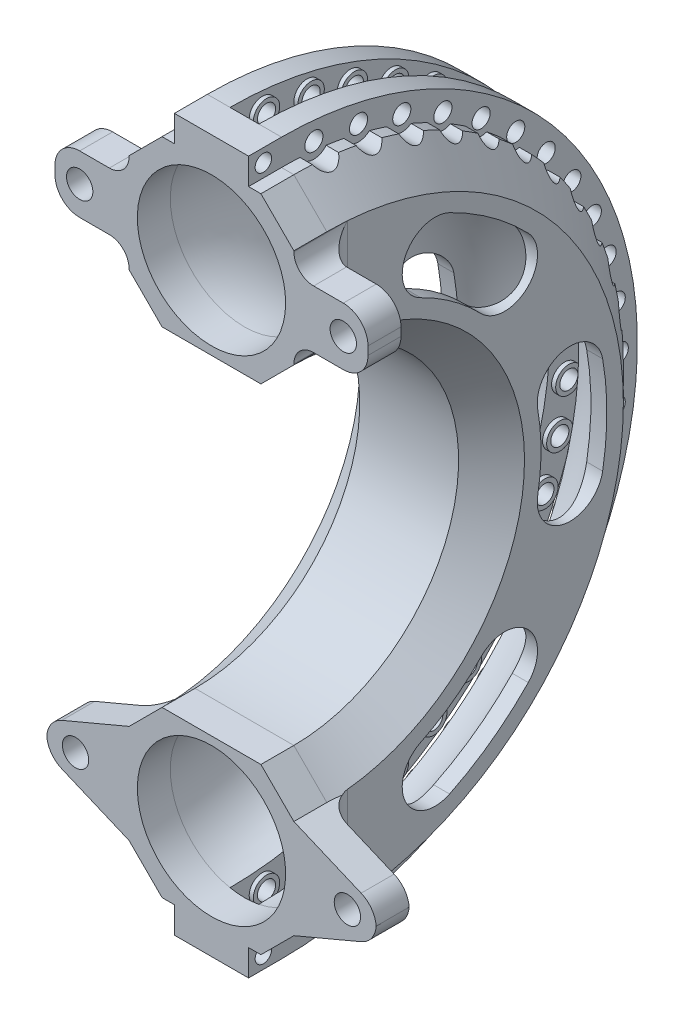
SolidWorks part; units mm, degrees
material "ABS"
ref_plane "前视基准面" through (0, 0, 0) normal (0, 0, 1) x (1, 0, 0)
ref_plane "上视基准面" through (0, 0, 0) normal (0, 1, 0) x (1, 0, 0)
ref_plane "右视基准面" through (0, 0, 0) normal (1, 0, 0) x (0, 0, -1)
sketch "草图1" plane through (0, 0, 0) normal (0, 0, 1) x (1, 0, 0)
  line L0 (0, 30) -> (0, -30) construction
  line L1 (0, 0) -> (57.2515, 0) construction
  line L2 (-10, 40) -> (10, 40)
  line L3 (-10, 40) -> (-10, 20)
  line L4 (-10, 20) -> (10, 20)
  line L5 (10, 40) -> (10, 20)
  line L6 (-10, 40) -> (10, 20) construction
  line L7 (-10, 20) -> (10, 40) construction
  circle A0 centre (0, 30) radius 9
  dimension "D2" = 18
  dimension "D1" = 60
  dimension "D3" = 20
sketch "草图2" plane through (0, 0, 0) normal (1, 0, 0) x (0, 0, -1)
  line L0 (0, 40) -> (0, 20) construction
  arc A0 (0, 30) -> (0, -30) centre (0, 0) cw
sweep "扫描2" add profiles "草图1" path "草图2"
chamfer "倒角1" distance 4 angle 45 4 edges at (-10, 0, -40) (-10, 0, -20) (10, 0, -20) (10, 0, -40)
sketch "草图9" plane through (0, 0, 0) normal (1, 0, 0) x (0, 0, -1)
  line L0 (0, 40) -> (0, 43.2)
  line L2 (0, -43.2) -> (0, -40)
  arc A0 (0, -43.2) -> (0, 43.2) centre (0, 0) ccw
  arc A1 (0, -40) -> (0, 40) centre (0, 0) ccw construction
  arc A2 (0, -40) -> (0, 40) centre (0, 0) ccw
  dimension "D1" = 3.2
extrude "凸台-拉伸1" add sketch "草图9" along normal blind 4.5 and the other way blind 4.5
sketch "草图10" plane through (0, 0, 0) normal (1, 0, 0) x (0, 0, -1)
  circle A0 centre (0, 0) radius 31.3466
  circle A1 centre (0, 0) radius 43.2
  arc A2 (0, -43.2) -> (0, 43.2) centre (0, 0) ccw construction
  dimension "D1" = 11.8534
extrude "切除-拉伸1" cut sketch "草图10" against normal blind 1.75 and the other way blind 1.75
sketch "草图11" plane through (0, 0, 0) normal (1, 0, 0) x (0, 0, -1)
  line L0 (3.9297, 40.8112) -> (0, 0) construction
  line L1 (0, 0) -> (0, 59.689) construction
  line L2 (0, 0) -> (3.9297, 40.8112) construction
  line L3 (0, 0) -> (9.3497, 39.9197) construction
  circle A0 centre (3.9297, 40.8112) radius 1.1
  circle A1 centre (9.3497, 39.9197) radius 1.1
  circle A2 centre (14.6019, 38.3117) radius 1.1
  circle A3 centre (19.5921, 36.016) radius 1.1
  circle A4 centre (24.2306, 33.0738) radius 1.1
  circle A5 centre (28.4342, 29.5381) radius 1.1
  circle A6 centre (32.1274, 25.4722) radius 1.1
  circle A7 centre (35.244, 20.949) radius 1.1
  circle A8 centre (37.728, 16.0499) radius 1.1
  circle A9 centre (39.5348, 10.8627) radius 1.1
  circle A10 centre (40.6321, 5.4805) radius 1.1
  circle A11 centre (41, 0) radius 1.1
  circle A12 centre (40.6321, -5.4805) radius 1.1
  circle A13 centre (39.5348, -10.8627) radius 1.1
  circle A14 centre (37.728, -16.0499) radius 1.1
  circle A15 centre (35.244, -20.949) radius 1.1
  circle A16 centre (32.1274, -25.4722) radius 1.1
  circle A17 centre (28.4342, -29.5381) radius 1.1
  circle A18 centre (24.2306, -33.0738) radius 1.1
  circle A19 centre (19.5921, -36.016) radius 1.1
  circle A20 centre (14.6019, -38.3117) radius 1.1
  circle A21 centre (9.3497, -39.9197) radius 1.1
  circle A22 centre (3.9297, -40.8112) radius 1.1
  dimension "D1" = 2.2
  dimension "D2" = 41
  dimension "D3" = 5.5
  dimension "D4" = 23
extrude "切除-拉伸2" cut sketch "草图11" against normal through all both and the other way through all
sketch "草图12" plane through (4.5, 0, 0) normal (1, 0, 0) x (0, 0, -1)
  circle A0 centre (3.9297, -40.8112) radius 1.9
  circle A1 centre (3.9297, -40.8112) radius 1.1
  circle A2 centre (3.9297, -40.8112) radius 1.1 construction
  circle A3 centre (19.5921, 36.016) radius 1.1
  circle A4 centre (19.5921, 36.016) radius 1.1 construction
  circle A5 centre (14.6019, 38.3117) radius 1.1
  circle A6 centre (14.6019, 38.3117) radius 1.1 construction
  circle A7 centre (9.3497, 39.9197) radius 1.1
  circle A8 centre (9.3497, 39.9197) radius 1.1 construction
  circle A9 centre (3.9297, 40.8112) radius 1.1
  circle A10 centre (3.9297, 40.8112) radius 1.1 construction
  circle A11 centre (41, 0) radius 1.1
  circle A12 centre (41, 0) radius 1.1 construction
  circle A13 centre (40.6321, 5.4805) radius 1.1
  circle A14 centre (40.6321, 5.4805) radius 1.1 construction
  circle A15 centre (39.5348, 10.8627) radius 1.1
  circle A16 centre (39.5348, 10.8627) radius 1.1 construction
  circle A17 centre (37.728, 16.0499) radius 1.1
  circle A18 centre (37.728, 16.0499) radius 1.1 construction
  circle A19 centre (35.244, 20.949) radius 1.1
  circle A20 centre (35.244, 20.949) radius 1.1 construction
  circle A21 centre (32.1274, 25.4722) radius 1.1
  circle A22 centre (32.1274, 25.4722) radius 1.1 construction
  circle A23 centre (28.4342, 29.5381) radius 1.1
  circle A24 centre (28.4342, 29.5381) radius 1.1 construction
  circle A25 centre (24.2306, 33.0738) radius 1.1
  circle A26 centre (24.2306, 33.0738) radius 1.1 construction
  circle A27 centre (19.5921, -36.016) radius 1.1
  circle A28 centre (19.5921, -36.016) radius 1.1 construction
  circle A29 centre (24.2306, -33.0738) radius 1.1
  circle A30 centre (24.2306, -33.0738) radius 1.1 construction
  circle A31 centre (28.4342, -29.5381) radius 1.1
  circle A32 centre (28.4342, -29.5381) radius 1.1 construction
  circle A33 centre (32.1274, -25.4722) radius 1.1
  circle A34 centre (32.1274, -25.4722) radius 1.1 construction
  circle A35 centre (35.244, -20.949) radius 1.1
  circle A36 centre (35.244, -20.949) radius 1.1 construction
  circle A37 centre (37.728, -16.0499) radius 1.1
  circle A38 centre (37.728, -16.0499) radius 1.1 construction
  circle A39 centre (39.5348, -10.8627) radius 1.1
  circle A40 centre (39.5348, -10.8627) radius 1.1 construction
  circle A41 centre (40.6321, -5.4805) radius 1.1
  circle A42 centre (40.6321, -5.4805) radius 1.1 construction
  circle A43 centre (9.3497, -39.9197) radius 1.1
  circle A44 centre (9.3497, -39.9197) radius 1.1 construction
  circle A45 centre (14.6019, -38.3117) radius 1.1
  circle A46 centre (14.6019, -38.3117) radius 1.1 construction
  circle A47 centre (19.5921, 36.016) radius 1.9
  circle A48 centre (14.6019, 38.3117) radius 1.9
  circle A49 centre (9.3497, 39.9197) radius 1.9
  circle A50 centre (3.9297, 40.8112) radius 1.9
  circle A51 centre (41, 0) radius 1.9
  circle A52 centre (40.6321, 5.4805) radius 1.9
  circle A53 centre (39.5348, 10.8627) radius 1.9
  circle A54 centre (37.728, 16.0499) radius 1.9
  circle A55 centre (35.244, 20.949) radius 1.9
  circle A56 centre (32.1274, 25.4722) radius 1.9
  circle A57 centre (28.4342, 29.5381) radius 1.9
  circle A58 centre (24.2306, 33.0738) radius 1.9
  circle A59 centre (19.5921, -36.016) radius 1.9
  circle A60 centre (24.2306, -33.0738) radius 1.9
  circle A61 centre (28.4342, -29.5381) radius 1.9
  circle A62 centre (32.1274, -25.4722) radius 1.9
  circle A63 centre (35.244, -20.949) radius 1.9
  circle A64 centre (37.728, -16.0499) radius 1.9
  circle A65 centre (39.5348, -10.8627) radius 1.9
  circle A66 centre (40.6321, -5.4805) radius 1.9
  circle A67 centre (9.3497, -39.9197) radius 1.9
  circle A68 centre (14.6019, -38.3117) radius 1.9
  circle A69 centre (3.9297, -40.8112) radius 0.1
  circle A70 centre (19.5921, 36.016) radius 0.1
  circle A71 centre (14.6019, 38.3117) radius 0.1
  circle A72 centre (9.3497, 39.9197) radius 0.1
  circle A73 centre (3.9297, 40.8112) radius 0.1
  circle A74 centre (41, 0) radius 0.1
  circle A75 centre (40.6321, 5.4805) radius 0.1
  circle A76 centre (39.5348, 10.8627) radius 0.1
  circle A77 centre (37.728, 16.0499) radius 0.1
  circle A78 centre (35.244, 20.949) radius 0.1
  circle A79 centre (32.1274, 25.4722) radius 0.1
  circle A80 centre (28.4342, 29.5381) radius 0.1
  circle A81 centre (24.2306, 33.0738) radius 0.1
  circle A82 centre (19.5921, -36.016) radius 0.1
  circle A83 centre (24.2306, -33.0738) radius 0.1
  circle A84 centre (28.4342, -29.5381) radius 0.1
  circle A85 centre (32.1274, -25.4722) radius 0.1
  circle A86 centre (35.244, -20.949) radius 0.1
  circle A87 centre (37.728, -16.0499) radius 0.1
  circle A88 centre (39.5348, -10.8627) radius 0.1
  circle A89 centre (40.6321, -5.4805) radius 0.1
  circle A90 centre (9.3497, -39.9197) radius 0.1
  circle A91 centre (14.6019, -38.3117) radius 0.1
  dimension "D1" = 0
  dimension "D2" = 0
  dimension "D3" = 0
  dimension "D4" = 0
  dimension "D5" = 0
  dimension "D6" = 0
  dimension "D7" = 0
  dimension "D8" = 0
  dimension "D9" = 0
  dimension "D10" = 0
  dimension "D11" = 0
  dimension "D12" = 0
  dimension "D13" = 0
  dimension "D14" = 0
  dimension "D15" = 0
  dimension "D16" = 0
  dimension "D17" = 0
  dimension "D18" = 0
  dimension "D19" = 0
  dimension "D20" = 0
  dimension "D21" = 0
  dimension "D22" = 0
  dimension "D23" = 0
  dimension "D24" = 0.8
  dimension "D25" = 1
extrude "切除-拉伸3" cut sketch "草图12" along normal through all
sketch "草图15" plane through (0, 0, 0) normal (1, 0, 0) x (0, 0, -1)
  line L0 (0, 24) -> (0, 36) construction
  line L1 (0, -24) -> (0, -36) construction
  arc A2 (0, 30) -> (0, -30) centre (0, 0) cw construction
  arc A3 (0, 26) -> (0, -26) centre (0, 0) cw
  arc A4 (0, 34) -> (0, -34) centre (0, 0) cw
  arc A5 (14.9046, 30.559) -> (11.3976, 23.3686) centre (13.1511, 26.9638) ccw
  arc A6 (24.4576, 23.6184) -> (18.7028, 18.0611) centre (21.5802, 20.8398) cw
  arc A7 (33.4835, 5.904) -> (25.605, 4.5149) centre (29.5442, 5.2094) ccw
  arc A8 (33.4835, -5.904) -> (25.605, -4.5149) centre (29.5442, -5.2094) cw
  arc A9 (24.4576, -23.6184) -> (18.7028, -18.0611) centre (21.5802, -20.8398) ccw
  arc A10 (14.9046, -30.559) -> (11.3976, -23.3686) centre (13.1511, -26.9638) cw
  point P35 (0, 0)
  dimension "D1" = 4
  dimension "D3" = 20
  dimension "D4" = 26
  dimension "D6" = 26
  dimension "D2" = 4
  dimension "D5" = 3
extrude "切除-拉伸4" cut sketch "草图15" against normal through all both and the other way through all contours A10 A4 A9 A3 | A8 A4 A7 A3 | A6 A4 A5 A3
mirror "镜向1" about plane through (0, 0, 0) normal (1, 0, 0) of "切除-拉伸3"
sketch "草图14" plane through (0, 0, 0) normal (0, 0, 1) x (1, 0, 0)
  line L0 (-4.5, 43.2) -> (4.5, 43.2)
  line L1 (-49.0988, 0) -> (52.224, 0) construction
  line L2 (4.5, -40) -> (4.5, -43.2)
  line L3 (6, -40) -> (4.5, -40)
  line L4 (10, -36) -> (6, -40)
  line L6 (6, -20) -> (10, -24)
  line L7 (-6, -20) -> (6, -20)
  line L8 (-10, -24) -> (-6, -20)
  line L10 (-6, -40) -> (-10, -36)
  line L11 (-4.5, -40) -> (-6, -40)
  line L12 (-4.5, -43.2) -> (-4.5, -40)
  line L13 (-4.5, -43.2) -> (4.5, -43.2)
  line L14 (0, 0) -> (0, 10.5985) construction
  line L15 (1.75, 43.2) -> (1.75, 38.8282)
  line L16 (-1.75, 38.8282) -> (-1.75, 43.2)
  line L17 (-1.75, 43.2) -> (-4.5, 43.2)
  line L18 (-4.5, 43.2) -> (-4.5, 40)
  line L19 (-4.5, 40) -> (-6, 40)
  line L20 (-6, 40) -> (-10, 36)
  line L21 (-10, 36) -> (-10, 24)
  line L22 (-10, 24) -> (-6, 20)
  line L23 (-6, 20) -> (6, 20)
  line L24 (6, 20) -> (10, 24)
  line L25 (10, 24) -> (10, 36)
  line L26 (10, 36) -> (6, 40)
  line L27 (6, 40) -> (4.5, 40)
  line L28 (4.5, 40) -> (4.5, 43.2)
  line L29 (4.5, 43.2) -> (1.75, 43.2)
  line L33 (-4.5, 43.2) -> (-4.5, 40)
  line L34 (-4.5, 40) -> (-6, 40)
  line L35 (-6, 40) -> (-10, 36)
  line L36 (-10, 36) -> (-10, 33.5)
  line L37 (-10, 24) -> (-6, 20)
  line L38 (-6, 20) -> (6, 20)
  line L39 (6, 20) -> (10, 24)
  line L40 (10, 24) -> (10, 26.5)
  line L41 (10, 36) -> (6, 40)
  line L42 (6, 40) -> (4.5, 40)
  line L43 (4.5, 40) -> (4.5, 43.2)
  line L45 (-19, 33.5) -> (-10, 33.5)
  line L46 (-19, 26.5) -> (-10, 26.5)
  line L47 (-10, 26.5) -> (-10, 24)
  line L48 (19, 26.5) -> (10, 26.5)
  line L49 (19, 33.5) -> (10, 33.5)
  line L50 (10, 33.5) -> (10, 36)
  line L51 (-10, -24) -> (-20, -28.2211)
  line L52 (-10, -36) -> (-20, -31.7789)
  line L53 (10, -36) -> (20, -31.7789)
  line L54 (10, -24) -> (20, -28.2211)
  line L55 (-19, 33.5) -> (-19, 26.5)
  line L56 (19, 33.5) -> (19, 26.5)
  line L57 (-20, -28.2211) -> (-20, -31.7789)
  line L58 (20, -28.2211) -> (20, -31.7789)
  circle A0 centre (0, 30) radius 9
  arc A1 (-1.75, 38.8282) -> (1.75, 38.8282) centre (0, 30) ccw
  arc A3 (-1.75, 38.8282) -> (1.75, 38.8282) centre (0, 30) ccw construction
  circle A4 centre (0, -30) radius 9
  circle A5 centre (-16, 30) radius 1.6
  circle A9 centre (16, 30) radius 1.6
  circle A10 centre (-16.5, -30) radius 1.6
  circle A13 centre (16.5, -30) radius 1.6
  point P61 (-19, 30)
  dimension "D2" = 32
  dimension "D3" = 3.2
  dimension "D4" = 3.5
  dimension "D5" = 3.2
  dimension "D7" = 3.5
  dimension "D9" = 3
  dimension "D6" = 33
  dimension "D8" = 3
  dimension "D10" = 3
  dimension "D1" = 0
extrude "凸台-拉伸2" add sketch "草图14" along normal blind 4
fillet "圆角1" radius 2.4 4 edges at (10, 33.5, 2) (10, 26.5, 2) (-10, 26.5, 2) (-10, 33.5, 2)
fillet "圆角2" radius 3 8 edges at (-19, 26.5, 2) (-19, 33.5, 2) (19, 26.5, 2) (19, 33.5, 2) (-20, -28.2211, 2) (-20, -31.7789, 2) (20, -28.2211, 2) (20, -31.7789, 2)
sketch "草图16" plane through (-1.75, 0, 0) normal (1, 0, 0) x (0, 0, -1)
  circle A0 centre (3.9297, -40.8112) radius 1.6
  circle A1 centre (3.9297, -40.8112) radius 1.1
  circle A2 centre (3.9297, -40.8112) radius 1.1
  circle A3 centre (19.5921, 36.016) radius 1.1
  circle A4 centre (19.5921, 36.016) radius 1.1
  circle A5 centre (14.6019, 38.3117) radius 1.1
  circle A6 centre (14.6019, 38.3117) radius 1.1
  circle A7 centre (9.3497, 39.9197) radius 1.1
  circle A8 centre (9.3497, 39.9197) radius 1.1
  circle A9 centre (3.9297, 40.8112) radius 1.1
  circle A10 centre (3.9297, 40.8112) radius 1.1
  circle A11 centre (41, 0) radius 1.1
  circle A12 centre (41, 0) radius 1.1
  circle A13 centre (40.6321, 5.4805) radius 1.1
  circle A14 centre (40.6321, 5.4805) radius 1.1
  circle A15 centre (39.5348, 10.8627) radius 1.1
  circle A16 centre (39.5348, 10.8627) radius 1.1
  circle A17 centre (37.728, 16.0499) radius 1.1
  circle A18 centre (37.728, 16.0499) radius 1.1
  circle A19 centre (35.244, 20.949) radius 1.1
  circle A20 centre (35.244, 20.949) radius 1.1
  circle A21 centre (32.1274, 25.4722) radius 1.1
  circle A22 centre (32.1274, 25.4722) radius 1.1
  circle A23 centre (28.4342, 29.5381) radius 1.1
  circle A24 centre (28.4342, 29.5381) radius 1.1
  circle A25 centre (24.2306, 33.0738) radius 1.1
  circle A26 centre (24.2306, 33.0738) radius 1.1
  circle A27 centre (19.5921, -36.016) radius 1.1
  circle A28 centre (19.5921, -36.016) radius 1.1
  circle A29 centre (24.2306, -33.0738) radius 1.1
  circle A30 centre (24.2306, -33.0738) radius 1.1
  circle A31 centre (28.4342, -29.5381) radius 1.1
  circle A32 centre (28.4342, -29.5381) radius 1.1
  circle A33 centre (32.1274, -25.4722) radius 1.1
  circle A34 centre (32.1274, -25.4722) radius 1.1
  circle A35 centre (35.244, -20.949) radius 1.1
  circle A36 centre (35.244, -20.949) radius 1.1
  circle A37 centre (37.728, -16.0499) radius 1.1
  circle A38 centre (37.728, -16.0499) radius 1.1
  circle A39 centre (39.5348, -10.8627) radius 1.1
  circle A40 centre (39.5348, -10.8627) radius 1.1
  circle A41 centre (40.6321, -5.4805) radius 1.1
  circle A42 centre (40.6321, -5.4805) radius 1.1
  circle A43 centre (9.3497, -39.9197) radius 1.1
  circle A44 centre (9.3497, -39.9197) radius 1.1
  circle A45 centre (14.6019, -38.3117) radius 1.1
  circle A46 centre (14.6019, -38.3117) radius 1.1
  circle A47 centre (19.5921, 36.016) radius 1.6
  circle A48 centre (14.6019, 38.3117) radius 1.6
  circle A49 centre (9.3497, 39.9197) radius 1.6
  circle A50 centre (3.9297, 40.8112) radius 1.6
  circle A51 centre (41, 0) radius 1.6
  circle A52 centre (40.6321, 5.4805) radius 1.6
  circle A53 centre (39.5348, 10.8627) radius 1.6
  circle A54 centre (37.728, 16.0499) radius 1.6
  circle A55 centre (35.244, 20.949) radius 1.6
  circle A56 centre (32.1274, 25.4722) radius 1.6
  circle A57 centre (28.4342, 29.5381) radius 1.6
  circle A58 centre (24.2306, 33.0738) radius 1.6
  circle A59 centre (19.5921, -36.016) radius 1.6
  circle A60 centre (24.2306, -33.0738) radius 1.6
  circle A61 centre (28.4342, -29.5381) radius 1.6
  circle A62 centre (32.1274, -25.4722) radius 1.6
  circle A63 centre (35.244, -20.949) radius 1.6
  circle A64 centre (37.728, -16.0499) radius 1.6
  circle A65 centre (39.5348, -10.8627) radius 1.6
  circle A66 centre (40.6321, -5.4805) radius 1.6
  circle A67 centre (9.3497, -39.9197) radius 1.6
  circle A68 centre (14.6019, -38.3117) radius 1.6
  dimension "D1" = 0
  dimension "D2" = 0
  dimension "D3" = 0
  dimension "D4" = 0
  dimension "D5" = 0
  dimension "D6" = 0
  dimension "D7" = 0
  dimension "D8" = 0
  dimension "D9" = 0
  dimension "D10" = 0
  dimension "D11" = 0
  dimension "D12" = 0
  dimension "D13" = 0
  dimension "D14" = 0
  dimension "D15" = 0
  dimension "D16" = 0
  dimension "D17" = 0
  dimension "D18" = 0
  dimension "D19" = 0
  dimension "D20" = 0
  dimension "D21" = 0
  dimension "D22" = 0
  dimension "D23" = 0
  dimension "D24" = 0.5
extrude "凸台-拉伸3" add sketch "草图16" along normal blind 0.5
mirror "镜向2" about plane through (0, 0, 0) normal (1, 0, 0) of "凸台-拉伸3"
sketch "草图18" plane through (-4.5, 0, 0) normal (-1, 0, 0) x (0, 0, 1)
  line L0 (4, 43.2) -> (0, 43.2) construction
  line L1 (4, 43.2) -> (4, 40) construction
  line L2 (0, 0) -> (51.2483, 0) construction
  circle A0 centre (2.2, 41.6) radius 1
  circle A1 centre (2.2, -41.6) radius 1
  dimension "D1" = 2
  dimension "D2" = 1.6
  dimension "D3" = 1.8
extrude "切除-拉伸5" cut sketch "草图18" against normal through all
fillet "圆角5" radius 2.5 4 edges at (-10, -30, 0) (10, -30, 0) (10, 30, 0) (-10, 30, 0)
